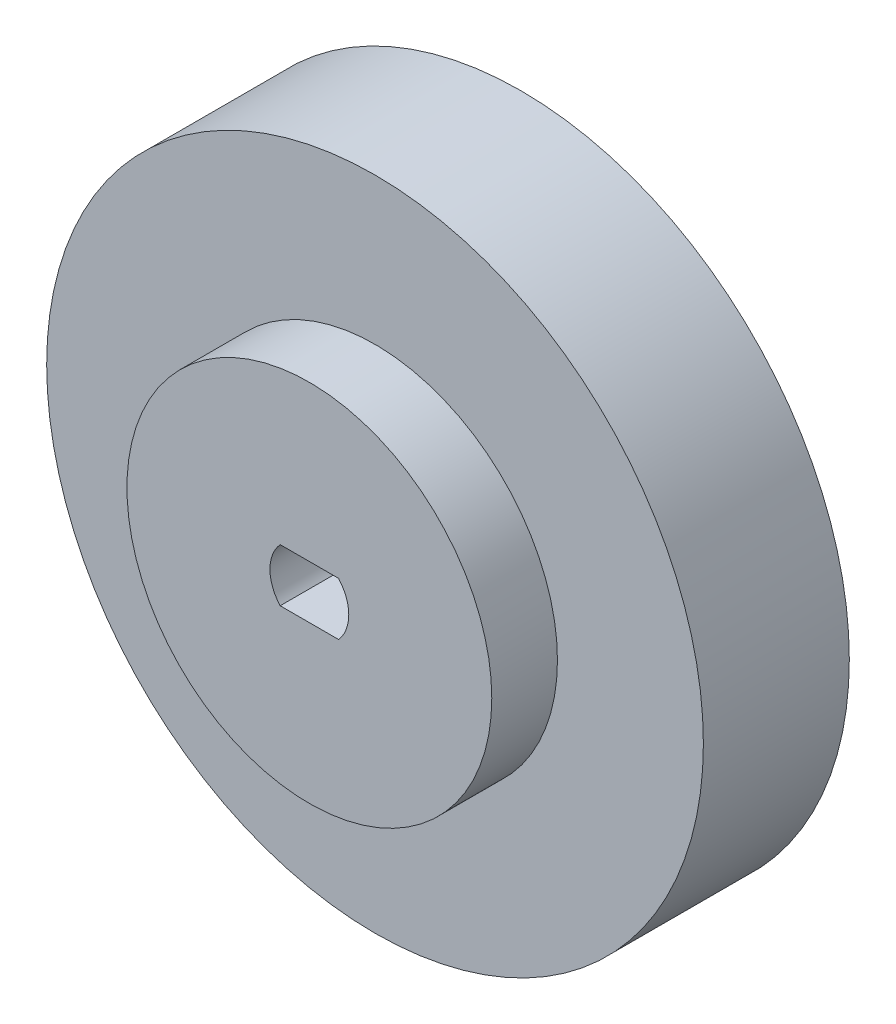
SolidWorks part; units mm, degrees
ref_plane "Front Plane" through (0, 0, 0) normal (0, 0, 1) x (1, 0, 0)
ref_plane "Top Plane" through (0, 0, 0) normal (0, 1, 0) x (1, 0, 0)
ref_plane "Right Plane" through (0, 0, 0) normal (1, 0, 0) x (0, 0, -1)
sketch "Sketch1" plane through (0, 0, 0) normal (0, 0, 1) x (1, 0, 0)
  line L0 (-34.1361, 0) -> (38.3541, 0) construction
  line L1 (0, 21.5067) -> (0, -21.6048) construction
  circle A0 centre (0, -0.049) radius 12.5
  dimension "D1" = 25
extrude "Boss-Extrude1" add sketch "Sketch1" along normal blind 19
sketch "Sketch2" plane through (0, 0, 19) normal (0, 0, 1) x (1, 0, 0)
  circle A0 centre (0, 0) radius 22.5
  dimension "D1" = 45
extrude "Boss-Extrude2" add sketch "Sketch2" against normal blind 10 from offset 4.5 offset against normal yes
sketch "Sketch3" plane through (0, 0, 19) normal (0, 0, 1) x (1, 0, 0)
  line L0 (-9.6925, 0) -> (15.432, 0) construction
  line L1 (-2, 1.8138) -> (2, 1.8138)
  line L2 (-2, -1.8138) -> (2, -1.8138)
  arc A0 (-2, 1.8138) -> (-2, -1.8138) centre (0, 0) ccw
  arc A1 (2, -1.8138) -> (2, 1.8138) centre (0, 0) ccw
  dimension "D1" = 5.4
  dimension "D2" = 4
extrude "Cut-Extrude1" cut sketch "Sketch3" against normal through all
